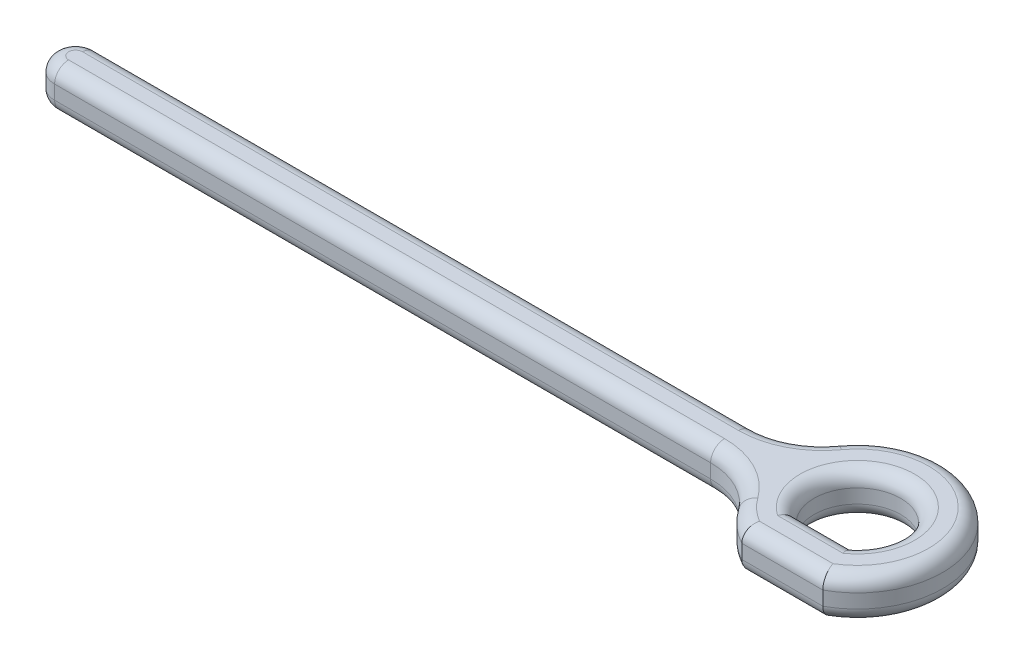
SolidWorks part; units mm, degrees
ref_plane "Front Plane" through (0, 0, 0) normal (0, 0, 1) x (1, 0, 0)
ref_plane "Top Plane" through (0, 0, 0) normal (0, 1, 0) x (1, 0, 0)
ref_plane "Right Plane" through (0, 0, 0) normal (1, 0, 0) x (0, 0, -1)
sketch "Sketch1" plane through (0, 0, 0) normal (0, 1, 0) x (1, 0, 0)
  line L0 (-2, -2.3685) -> (2, -2.3685)
  line L1 (-2.8963, -5.3685) -> (2.8963, -5.3685)
  line L2 (-1000, 0) -> (49000, 0) construction
  line L3 (-8.9978, -1.5) -> (-55.9127, -1.5)
  line L4 (-8.9978, 1.5) -> (-55.9127, 1.5)
  arc A0 (2, -2.3685) -> (-2, -2.3685) centre (0, 0) ccw
  arc A1 (2.8963, -5.3685) -> (-4.9447, 3.5721) centre (0, 0) ccw
  arc A2 (-55.9127, -1.5) -> (-55.9127, 1.5) centre (-55.9127, 0) cw
  arc A3 (-4.9447, -3.5721) -> (-2.8963, -5.3685) centre (0, 0) ccw
  arc A4 (2.8963, -5.3685) -> (-2.8963, -5.3685) centre (0, 0) ccw construction
  arc A5 (-8.9978, 1.5) -> (-4.9447, 3.5721) centre (-8.9978, 6.5) ccw
  arc A6 (-8.9978, -1.5) -> (-4.9447, -3.5721) centre (-8.9978, -6.5) cw
  point P16 (-5.9127, 1.5)
  point P19 (-5.9127, -1.5)
  dimension "D1" = 6.2
  dimension "D4" = 1.5
  dimension "D6" = 5
  dimension "D2" = 4
  dimension "D5" = 50
  dimension "D3" = 3
extrude "Boss-Extrude1" add sketch "Sketch1" along normal blind 3
fillet "Fillet1" radius 1 20 edges at (4.5861, 0, -4.0221) (-6.7218, 0, -2.0481) (-32.4552, 0, -1.5) (-57.4127, 0, 0) (-4.0221, 0, 4.5861) (-6.7218, 0, 2.0481) (4.5861, 3, -4.0221) (-6.7218, 3, -2.0481) (-32.4552, 3, -1.5) (-57.4127, 3, 0) (-4.0221, 3, 4.5861) (-6.7218, 3, 2.0481) (0, 0, 2.3685) (0, 0, -3.1) (0, 0, 5.3685) (0, 3, 5.3685) (0, 3, -3.1) (0, 3, 2.3685) (-32.4552, 0, 1.5) (-32.4552, 3, 1.5)
ref_axis "Axis1" through (0, 2, 0) along (0, -1, 0)
